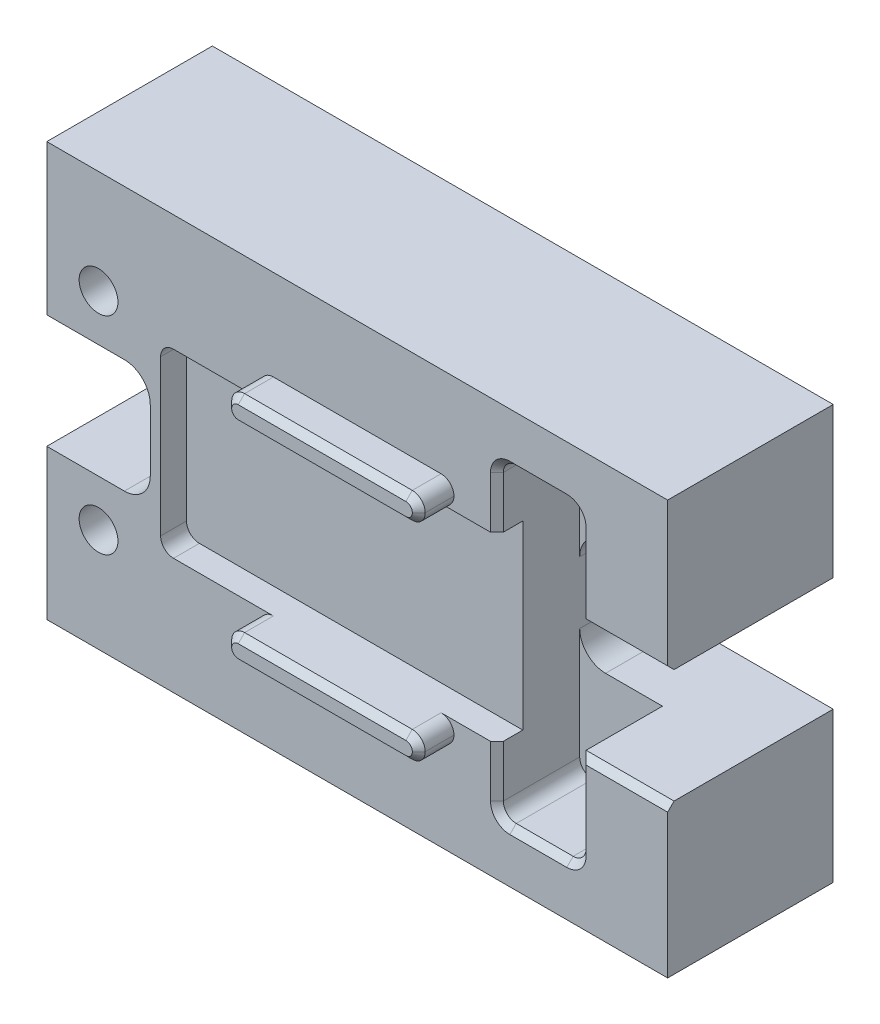
SolidWorks part; units mm, degrees
ref_plane "Front Plane" through (0, 0, 0) normal (1, 0, 0) x (0, 1, 0)
ref_plane "Top Plane" through (0, 0, 0) normal (0, 0, 1) x (0, 1, 0)
ref_plane "Right Plane" through (0, 0, 0) normal (0, 1, 0) x (-1, 0, 0)
sketch "Sketch1" plane through (0, 0, 0) normal (0, 0, 1) x (0, 1, 0)
  line L0 (-25.4, 38.1) -> (25.4, -38.1) construction
  line L1 (-25.4, 38.1) -> (25.4, 38.1)
  line L2 (-25.4, 38.1) -> (-25.4, -38.1)
  line L3 (-25.4, -38.1) -> (25.4, -38.1)
  line L4 (25.4, 38.1) -> (25.4, -38.1)
  line L5 (25.4, 38.1) -> (-25.4, -38.1) construction
  dimension "D1" = 76.2
  dimension "D2" = 50.8
extrude "Boss-Extrude1" add sketch "Sketch1" against normal blind 13.97 contours L2 L3 L4 L1
sketch "Sketch2" plane through (0, 0, 0) normal (0, 0, 1) x (1, 0, 0)
  line L4 (-38.1, 25.4) -> (-38.1, -25.4)
  line L5 (-38.1, -25.4) -> (38.1, -25.4)
  line L6 (38.1, -25.4) -> (38.1, 25.4)
  line L7 (38.1, 25.4) -> (-38.1, 25.4)
  line L8 (-38.1, 25.4) -> (-38.1, -25.4)
  line L9 (-38.1, -25.4) -> (38.1, -25.4)
  line L10 (38.1, -25.4) -> (38.1, 25.4)
  line L11 (38.1, 25.4) -> (-38.1, 25.4)
  dimension "D1" = 0
extrude "Boss-Extrude2" add sketch "Sketch2" along normal blind 6.35
sketch "Sketch3" plane through (0, 0, 6.35) normal (0, 0, 1) x (1, 0, 0)
  line L0 (38.1, 6.985) -> (38.1, -6.985)
  line L2 (38.1, -6.985) -> (27.305, -6.985)
  line L3 (27.305, -6.985) -> (27.305, -19.05)
  line L4 (27.305, -19.05) -> (17.145, -19.05)
  line L5 (17.145, -19.05) -> (17.145, 19.05)
  line L6 (17.145, 19.05) -> (27.305, 19.05)
  line L7 (27.305, 19.05) -> (27.305, 6.985)
  line L8 (27.305, 6.985) -> (38.1, 6.985)
  line L9 (0, 0) -> (17.145, 0) construction
  line L10 (17.145, 0) -> (38.1, 0) construction
  line L11 (38.1, -25.4) -> (38.1, 25.4) construction
  dimension "D1" = 13.97
  dimension "D2" = 38.1
  dimension "D3" = 10.16
  dimension "D4" = 0
  dimension "D5" = 10.795
extrude "Cut-Extrude1" cut sketch "Sketch3" against normal blind 10.16
sketch "Sketch4" plane through (0, 0, 6.35) normal (0, 0, 1) x (1, 0, 0)
  line L0 (-38.1, 6.985) -> (-25.4, 6.985)
  line L2 (-25.4, 6.985) -> (-25.4, -6.985)
  line L4 (-25.4, -6.985) -> (-38.1, -6.985)
  line L5 (-38.1, -6.985) -> (-38.1, 6.985)
  line L6 (38.1, 6.985) -> (17.145, 6.985)
  line L7 (38.1, -25.4) -> (38.1, -6.985) construction
  line L8 (17.145, 6.985) -> (17.145, -6.985)
  line L9 (17.145, -6.985) -> (38.1, -6.985)
  line L10 (38.1, 6.985) -> (38.1, -6.985)
  line L11 (17.145, 19.05) -> (17.145, -19.05) construction
  line L13 (38.1, 6.985) -> (27.305, 6.985) construction
  line L14 (27.305, -6.985) -> (38.1, -6.985) construction
  line L15 (-38.1, 25.4) -> (-38.1, -25.4) construction
  dimension "D1" = 12.7
extrude "Cut-Extrude2" cut sketch "Sketch4" against normal through all
sketch "Sketch6" plane through (0, 0, 0) normal (0, 1, 0) x (-1, 0, 0)
  line L0 (-17.145, -3.81) -> (-17.145, 6.35) construction
  line L1 (-17.145, -3.81) -> (-27.305, -3.81) construction
  line L2 (37.2484, 6.35) -> (38.1, 6.35)
  line L3 (-38.1, 6.35) -> (38.1, 6.35) construction
  line L4 (38.1, 6.35) -> (38.1, -13.97)
  line L5 (38.1, -13.97) -> (35.4867, -13.97)
  line L6 (38.1, -13.97) -> (-38.1, -13.97) construction
  circle A0 centre (-22.225, 1.27) radius 5.08 construction
  arc A1 (35.4867, -13.97) -> (37.2484, 6.35) centre (-22.225, 1.27) ccw
  dimension "D1" = 10.16
  dimension "D2" = 119.38
sketch "Sketch8" plane through (0, 0, 6.35) normal (0, 0, 1) x (1, 0, 0)
  line L0 (-31.75, 12.7) -> (-31.75, -12.7) construction
  line L1 (0, 0) -> (-31.75, 0) construction
  circle A0 centre (-31.75, 12.7) radius 2.3812
  circle A1 centre (-31.75, -12.7) radius 2.3812
  dimension "D2" = 4.7625
  dimension "D3" = 31.75
  dimension "D1" = 25.4
extrude "Cut-Extrude4" cut sketch "Sketch8" against normal through all
sketch "Sketch10" plane through (0, 0, 6.35) normal (0, 0, 1) x (1, 0, 0)
  line L0 (-29.3687, 12.7) -> (-11.8745, 12.7) construction
  line L1 (-11.8745, 14.2875) -> (11.8745, 14.2875)
  line L2 (11.8745, 14.2875) -> (11.8745, 11.1125)
  line L3 (11.8745, 11.1125) -> (-11.8745, 11.1125)
  line L4 (-11.8745, 11.1125) -> (-11.8745, 14.2875)
  line L5 (0, 11.1125) -> (0, 0) construction
  circle A0 centre (-31.75, 12.7) radius 2.3812 construction
  dimension "D1" = 3.175
  dimension "D2" = 23.749
extrude "Boss-Extrude4" add sketch "Sketch10" along normal blind 4.318 contours L1 L2 L3 L4
sketch "Sketch14" plane through (0, 0, 6.35) normal (0, 0, 1) x (1, 0, 0)
  line L0 (11.8745, 11.1125) -> (15.113, 11.1125)
  line L1 (13.5255, 11.1125) -> (13.5255, 15.9385) construction
  line L2 (-13.462, 15.9385) -> (-13.462, 11.1125) construction
  line L3 (13.5255, 17.526) -> (-13.462, 17.526)
  line L4 (-13.462, 15.9385) -> (13.5255, 15.9385) construction
  line L5 (-11.8745, 14.2875) -> (11.8745, 14.2875) construction
  line L6 (11.8745, 14.2875) -> (11.8745, 11.1125) construction
  line L7 (15.113, 11.1125) -> (15.113, 15.9385)
  line L8 (11.8745, 11.1125) -> (11.8745, 14.2875)
  line L9 (11.8745, 14.2875) -> (-11.8745, 14.2875)
  line L10 (-11.8745, 14.2875) -> (-11.8745, 11.1125)
  line L11 (-15.0495, 15.9385) -> (-15.0495, 11.1125)
  line L12 (-15.0495, 11.1125) -> (-11.8745, 11.1125)
  arc A1 (-13.462, 17.526) -> (-15.0495, 15.9385) centre (-13.462, 15.9385) ccw
  arc A2 (15.113, 15.9385) -> (13.5255, 17.526) centre (13.5255, 15.9385) ccw
  dimension "D2" = 1.5875
  dimension "D1" = 1.5875
  dimension "D3" = 1.651
  dimension "D4" = 1.651
extrude "Cut-Extrude6" [suppressed] cut sketch "Sketch14" against normal blind 2.54
sketch "Sketch11" plane through (0, 0, 6.35) normal (0, 0, 1) x (1, 0, 0)
  line L0 (-24.13, 11.1125) -> (17.145, 11.1125)
  line L1 (11.8745, 11.1125) -> (-11.8745, 11.1125) construction
  line L2 (-24.13, 11.1125) -> (-24.13, -11.1125)
  line L3 (-24.13, -11.1125) -> (17.145, -11.1125)
  line L4 (17.145, -11.1125) -> (17.145, 11.1125)
  line L5 (0, 0) -> (-24.13, 0) construction
  line L6 (17.145, 19.05) -> (17.145, 6.985) construction
  line L7 (17.145, 19.05) -> (17.145, -19.05) construction
  line L8 (-25.4, -6.985) -> (-25.4, 6.985) construction
  dimension "D1" = 1.27
extrude "Cut-Extrude5" cut sketch "Sketch11" against normal blind 3.175
mirror "Mirror1" about plane through (0, 0, 0) normal (0, 1, 0) of "Cut-Extrude6", "Boss-Extrude4"
fillet "Fillet2" radius 3.175 4 edges at (17.145, -6.985, -8.89) (17.145, 6.985, -8.89) (-25.4, -6.985, -3.81) (-25.4, 6.985, -3.81)
fillet "Fillet3" radius 1.5875 14 edges at (-24.13, -11.1125, 4.7625) (-24.13, 11.1125, 4.7625) (17.145, -19.05, 1.27) (27.305, -19.05, 1.27) (11.8745, 14.2875, 8.509) (11.8745, -11.1125, 8.509) (11.8745, -14.2875, 8.509) (11.8745, 11.1125, 8.509) (17.145, 19.05, 1.27) (-11.8745, -14.2875, 8.509) (-11.8745, -11.1125, 8.509) (-11.8745, 11.1125, 8.509) (-11.8745, 14.2875, 8.509) (27.305, 19.05, 1.27)
chamfer "Chamfer3" distance 0.7874 angle 45 24 edges at (0, -11.1125, 10.668) (-11.4095, -11.5775, 10.668) (11.4095, -11.5775, 10.668) (-11.4095, -13.8225, 10.668) (11.4095, -13.8225, 10.668) (0, -14.2875, 10.668) (0, 14.2875, 10.668) (11.4095, 13.8225, 10.668) (-11.4095, 13.8225, 10.668) (11.4095, 11.5775, 10.668) (-11.4095, 11.5775, 10.668) (0, 11.1125, 10.668) (17.145, -14.2875, 6.35) (17.61, -18.585, 6.35) (22.225, -19.05, 6.35) (26.84, -18.585, 6.35) (32.7025, -6.985, 6.35) (27.305, -12.2238, 6.35) (17.145, 14.2875, 6.35) (17.61, 18.585, 6.35) (22.225, 19.05, 6.35) (26.84, 18.585, 6.35) (32.7025, 6.985, 6.35) (27.305, 12.2238, 6.35)
